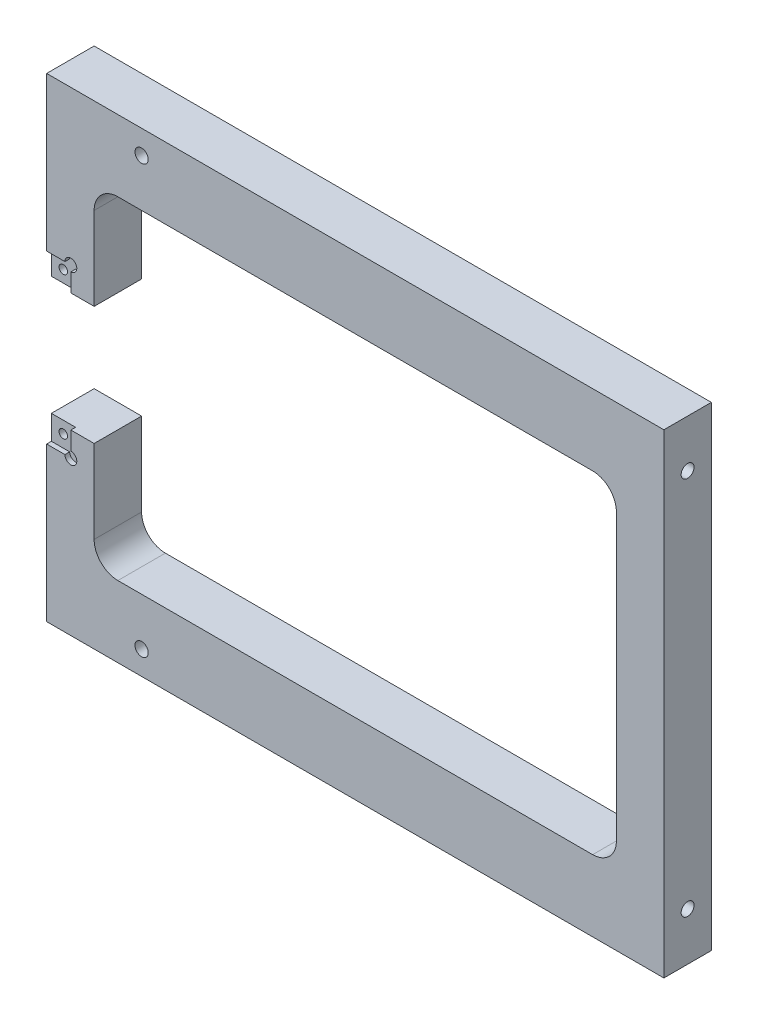
SolidWorks part; units mm, degrees
material "1060 Alloy"
ref_plane "Front Plane" through (0, 0, 0) normal (0, 0, 1) x (1, 0, 0)
ref_plane "Top Plane" through (0, 0, 0) normal (0, 1, 0) x (1, 0, 0)
ref_plane "Right Plane" through (0, 0, 0) normal (1, 0, 0) x (0, 0, -1)
sketch "Sketch1" plane through (0, 0, 0) normal (0, 0, 1) x (1, 0, 0)
  line L0 (82.55, 63.5) -> (-82.55, -63.5) construction
  line L1 (-82.55, 63.5) -> (82.55, 63.5)
  line L2 (-82.55, 63.5) -> (-82.55, -63.5)
  line L3 (-82.55, -63.5) -> (82.55, -63.5)
  line L4 (82.55, 63.5) -> (82.55, -63.5)
  point P4 (0, 0)
  dimension "D1" = 127
  dimension "D2" = 165.1
extrude "Boss-Extrude1" add sketch "Sketch1" along normal blind 12.7
sketch "Sketch2" plane through (0, 0, 0) normal (0, 0, 1) x (1, 0, 0)
  line L0 (-82.55, -15.875) -> (-69.85, -15.875)
  line L1 (-82.55, 63.5) -> (-82.55, -63.5) construction
  line L2 (-69.85, -15.875) -> (-69.85, -44.45)
  line L3 (-69.85, -44.45) -> (69.85, -44.45)
  line L4 (69.85, -44.45) -> (69.85, 44.45)
  line L5 (69.85, 44.45) -> (-69.85, 44.45)
  line L6 (-69.85, 44.45) -> (-69.85, 15.875)
  line L7 (-69.85, 15.875) -> (-82.55, 15.875)
  line L8 (-82.55, 15.875) -> (-82.55, -15.875)
  line L9 (-82.55, -63.5) -> (82.55, -63.5) construction
  line L10 (82.55, -63.5) -> (82.55, 63.5) construction
  line L11 (82.55, 63.5) -> (-82.55, 63.5) construction
  dimension "D1" = 31.75
  dimension "D2" = 12.7
  dimension "D3" = 12.7
  dimension "D4" = 19.05
  dimension "D5" = 12.7
  dimension "D6" = 19.05
  dimension "D7" = 47.625
extrude "Cut-Extrude1" cut sketch "Sketch2" along normal through all
sketch "Sketch3" plane through (0, 0, 12.7) normal (0, 0, 1) x (1, 0, 0)
  line L0 (-82.55, 63.5) -> (-82.55, 15.875) construction
  line L1 (-82.55, 22.352) -> (-76.073, 22.352)
  line L2 (-82.55, 22.352) -> (-82.55, 15.875)
  line L3 (-82.55, 15.875) -> (-76.073, 15.875)
  line L4 (-76.073, 22.352) -> (-76.073, 15.875)
  line L5 (-69.85, 15.875) -> (-82.55, 15.875) construction
  line L7 (-82.55, -15.875) -> (-76.073, -15.875)
  line L8 (-82.55, -15.875) -> (-82.55, -22.352)
  line L9 (-82.55, -22.352) -> (-76.073, -22.352)
  line L10 (-76.073, -15.875) -> (-76.073, -22.352)
  dimension "D1" = 6.477
  dimension "D2" = 6.477
  dimension "D3" = 6.477
  dimension "D4" = 6.477
extrude "Cut-Extrude2" cut sketch "Sketch3" against normal blind 1.27 contours L3 L4 L1 L2
sketch "Sketch4" plane through (0, 0, 12.7) normal (0, 0, 1) x (1, 0, 0)
  line L1 (-82.55, -15.875) -> (-76.073, -15.875)
  line L2 (-82.55, -15.875) -> (-82.55, -22.352)
  line L3 (-82.55, -22.352) -> (-76.073, -22.352)
  line L4 (-76.073, -15.875) -> (-76.073, -22.352)
  dimension "D1" = 6.477
  dimension "D2" = 6.477
extrude "Cut-Extrude3" cut sketch "Sketch4" against normal blind 1.27
sketch "Sketch5" plane through (-82.55, 0, 0) normal (-1, 0, 0) x (0, 0, 1)
  line L0 (12.7, 63.5) -> (12.7, 22.352) construction
  line L2 (12.7, -22.352) -> (12.7, -63.5) construction
  line L3 (12.7, -63.5) -> (0, -63.5) construction
  line L4 (12.7, 63.5) -> (0, 63.5) construction
  point P0 (6.35, 50.8)
  point P6 (6.35, -50.6899)
  point P9 (6.35, -63.5)
  dimension "D1" = 6.35
  dimension "D2" = 12.7
  dimension "D3" = 6.35
  dimension "D4" = 12.8101
hole_wizard "#8-32 Tapped Hole1" positions "Sketch7" profile "Sketch6" tap size "#8-32" standard "ANSI Inch"
sketch "Sketch7" plane through (-82.55, 0, 0) normal (-1, 0, 0) x (0, 0, 1)
  point P0 (6.35, 50.8)
sketch "Sketch6" plane through (-82.55, 50.8, 6.35) normal (0, 1, 0) x (0, 0, 1)
  line L0 (0, 0) -> (0, 13.7378)
  line L1 (0, 13.7378) -> (1.7272, 12.7)
  line L2 (1.7272, 12.7) -> (1.7272, 0)
  line L5 (1.7272, 0) -> (0, 0)
  line L10 (0, 13.7378) -> (-1.7272, 12.7) construction
  line L11 (0, -6.35) -> (0, 107.95) construction
  dimension "Tap Drill Dia." = 3.4544
  dimension "Tap Drill Depth" = 12.7
  dimension "Drill Angle" = 118
cosmetic thread "Hole Thread1" parameters "D1"=8.382, "D2"=4.1656
hole_wizard "#8-32 Tapped Hole2" positions "Sketch10" profile "Sketch8" tap size "#8-32" standard "ANSI Inch"
sketch "Sketch10" plane through (-82.55, 0, 0) normal (-1, 0, 0) x (0, 0, 1)
  point P0 (6.35, -50.6899)
sketch "Sketch8" plane through (-82.55, -50.6899, 6.35) normal (0, 1, 0) x (0, 0, 1)
  line L0 (0, 0) -> (0, 13.7378)
  line L1 (0, 13.7378) -> (1.7272, 12.7)
  line L2 (1.7272, 12.7) -> (1.7272, 0)
  line L5 (1.7272, 0) -> (0, 0)
  line L10 (0, 13.7378) -> (-1.7272, 12.7) construction
  line L11 (0, -6.35) -> (0, 107.95) construction
  dimension "Tap Drill Dia." = 3.4544
  dimension "Tap Drill Depth" = 12.7
  dimension "Drill Angle" = 118
cosmetic thread "Hole Thread2" parameters "D1"=8.382, "D2"=4.1656
hole_wizard "#8-32 Tapped Hole3" positions "Sketch12" profile "Sketch11" tap size "#8-32" standard "ANSI Inch"
sketch "Sketch12" plane through (82.55, 0, 0) normal (1, 0, 0) x (0, 0, -1)
  point P0 (-6.35, 50.8)
sketch "Sketch11" plane through (82.55, 50.8, 6.35) normal (0, 1, 0) x (0, 0, -1)
  line L0 (0, 0) -> (0, 13.7378)
  line L1 (0, 13.7378) -> (1.7272, 12.7)
  line L2 (1.7272, 12.7) -> (1.7272, 0)
  line L5 (1.7272, 0) -> (0, 0)
  line L10 (0, 13.7378) -> (-1.7272, 12.7) construction
  line L11 (0, -6.35) -> (0, 107.95) construction
  dimension "Tap Drill Dia." = 3.4544
  dimension "Tap Drill Depth" = 12.7
  dimension "Drill Angle" = 118
cosmetic thread "Hole Thread3" parameters "D1"=8.382, "D2"=4.1656
hole_wizard "#8-32 Tapped Hole4" positions "Sketch14" profile "Sketch13" tap size "#8-32" standard "ANSI Inch"
sketch "Sketch14" plane through (82.55, 0, 0) normal (1, 0, 0) x (0, 0, -1)
  point P0 (-6.35, -50.6899)
sketch "Sketch13" plane through (82.55, -50.6899, 6.35) normal (0, 1, 0) x (0, 0, -1)
  line L0 (0, 0) -> (0, 13.7378)
  line L1 (0, 13.7378) -> (1.7272, 12.7)
  line L2 (1.7272, 12.7) -> (1.7272, 0)
  line L5 (1.7272, 0) -> (0, 0)
  line L10 (0, 13.7378) -> (-1.7272, 12.7) construction
  line L11 (0, -6.35) -> (0, 107.95) construction
  dimension "Tap Drill Dia." = 3.4544
  dimension "Tap Drill Depth" = 12.7
  dimension "Drill Angle" = 118
cosmetic thread "Hole Thread4" parameters "D1"=8.382, "D2"=4.1656
sketch "Sketch15" plane through (0, 0, 11.43) normal (0, 0, 1) x (1, 0, 0)
  line L0 (-82.55, 22.352) -> (-82.55, 15.875) construction
  line L1 (-82.55, 15.875) -> (-76.073, 15.875) construction
  line L2 (-76.073, -15.875) -> (-82.55, -15.875) construction
  line L3 (-82.55, -15.875) -> (-82.55, -22.352) construction
  point P0 (-79.375, 19.05)
  point P5 (-79.375, -19.05)
  dimension "D1" = 3.175
  dimension "D2" = 3.175
  dimension "D3" = 3.175
  dimension "D4" = 3.175
hole_wizard "#4-40 Tapped Hole1" positions "Sketch17" profile "Sketch16" tap size "#4-40" standard "ANSI Inch" end condition through all
sketch "Sketch17" plane through (0, 0, 11.43) normal (0, 0, 1) x (1, 0, 0)
  point P0 (-79.375, 19.05)
sketch "Sketch16" plane through (-79.375, 19.05, 11.43) normal (1, 0, 0) x (0, -1, 0)
  line L0 (0, 0) -> (0, 11.43)
  line L1 (0, 11.43) -> (1.1303, 11.43)
  line L2 (1.1303, 11.43) -> (1.1303, 0)
  line L5 (1.1303, 0) -> (0, 0)
  line L11 (0, -6.35) -> (0, 107.95) construction
  dimension "Thru Tap Drill Dia." = 2.2606
  dimension "Thru Tap Drill Depth" = 11.43
cosmetic thread "Hole Thread5" parameters "D2"=2.8448
hole_wizard "#4-40 Tapped Hole2" positions "Sketch19" profile "Sketch18" tap size "#4-40" standard "ANSI Inch" end condition through all
sketch "Sketch19" plane through (0, 0, 11.43) normal (0, 0, 1) x (1, 0, 0)
  point P0 (-79.375, -19.05)
sketch "Sketch18" plane through (-79.375, -19.05, 11.43) normal (1, 0, 0) x (0, -1, 0)
  line L0 (0, 0) -> (0, 11.43)
  line L1 (0, 11.43) -> (1.1303, 11.43)
  line L2 (1.1303, 11.43) -> (1.1303, 0)
  line L5 (1.1303, 0) -> (0, 0)
  line L11 (0, -6.35) -> (0, 107.95) construction
  dimension "Thru Tap Drill Dia." = 2.2606
  dimension "Thru Tap Drill Depth" = 11.43
cosmetic thread "Hole Thread6" parameters "D2"=2.8448
sketch "Sketch20" plane through (0, 0, 12.7) normal (0, 0, 1) x (1, 0, 0)
  line L0 (-82.55, -22.352) -> (-82.55, -63.5) construction
  line L1 (-82.55, -63.5) -> (82.55, -63.5) construction
  line L2 (-82.55, 63.5) -> (-82.55, 22.352) construction
  line L3 (82.55, 63.5) -> (-82.55, 63.5) construction
  circle A0 centre (-57.15, -57.15) radius 1.778
  point P0 (-57.15, -57.15)
  point P5 (-57.15, 57.15)
  dimension "D1" = 25.4
  dimension "D2" = 6.35
  dimension "D3" = 25.4
  dimension "D4" = 6.35
extrude "Cut-Extrude4" cut sketch "Sketch20" against normal through all
sketch "Sketch21" plane through (0, 0, 12.7) normal (0, 0, 1) x (1, 0, 0)
  line L0 (-82.55, 63.5) -> (-82.55, 22.352) construction
  line L1 (82.55, 63.5) -> (-82.55, 63.5) construction
  circle A0 centre (-57.15, 57.15) radius 1.778
  point P0 (-57.15, 57.15)
  dimension "D1" = 25.4
  dimension "D2" = 6.35
extrude "Cut-Extrude5" cut sketch "Sketch21" against normal through all
fillet "Fillet4" radius 6.35 1 edges at (-69.85, -44.45, 6.35)
fillet "Fillet5" radius 6.35 3 edges at (69.85, -44.45, 6.35) (69.85, 44.45, 6.35) (-69.85, 44.45, 6.35)
sketch "Sketch24" plane through (0, 0, 12.7) normal (0, 0, 1) x (1, 0, 0)
  circle A0 centre (-76.073, -22.352) radius 1.5875
  circle A1 centre (-76.073, 22.352) radius 1.5875
extrude "Cut-Extrude6" cut sketch "Sketch24" against normal blind 1.27
